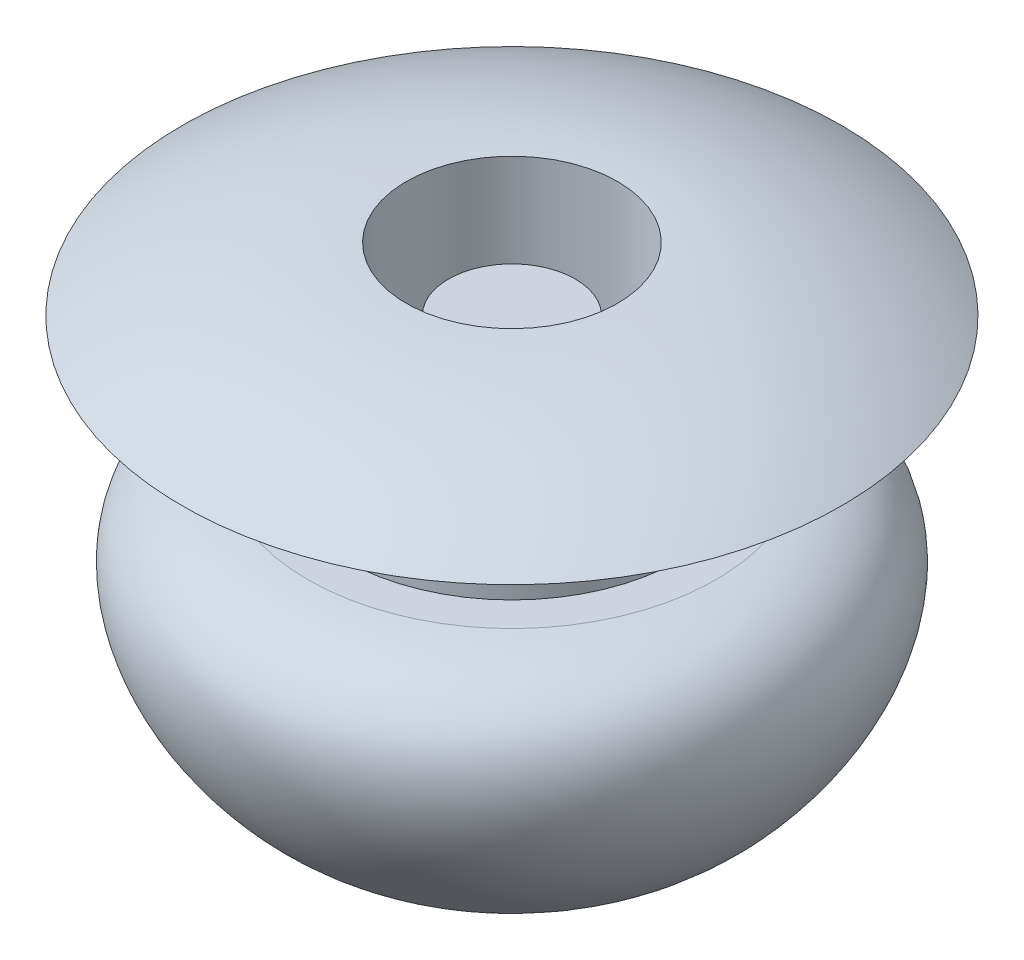
SolidWorks part; units mm, degrees
material "AISI 316 Stal nierdzewna odprężona (SS)"
ref_plane "Płaszczyzna przednia" through (0, 0, 0) normal (0, 0, 1) x (1, 0, 0)
ref_plane "Płaszczyzna górna" through (0, 0, 0) normal (0, 1, 0) x (1, 0, 0)
ref_plane "Płaszczyzna prawa" through (0, 0, 0) normal (1, 0, 0) x (0, 0, -1)
sketch "Szkic1" plane through (0, 0, 0) normal (1, 0, 0) x (0, 0, -1)
  line L1 (0, 0) -> (-0.75, 0)
  line L2 (-0.75, 0) -> (-0.75, -1.7007)
  line L3 (-0.75, -1.7007) -> (-1.25, -1.7007)
  line L4 (-1.25, -1.7007) -> (-1.25, 0.75)
  line L5 (-3.9, 0) -> (-2, 0)
  line L6 (-2, 0) -> (-2, -1.5)
  line L7 (-2, -1.5) -> (-2.4139, -1.5)
  line L8 (0, 0) -> (0, 0.4842) construction
  line L9 (0, -1.7007) -> (0, 0)
  line L10 (0, -1.7007) -> (0, -3.2007)
  line L11 (-10.4007, -1.5) -> (-6.4007, -1.5) construction
  arc A0 (-1.25, 0.75) -> (-3.9, 0) centre (-1.25, -4.3067) ccw
  ellipse E0 centre (0, -2.4507) end of major axis (1.75, -2.4507) minor radius 0.75 (-0.956, -3.0789) -> (0, -3.2007) ccw
  spline S0 degree 3 poles (-2.4139, -1.5) (-3.8675, -1.6697) (-3.5289, -3.802) (-1.084, -5.3735) (-0.2718, -3.3749) (-0.956, -3.0789) knots 0 0 0 0 0.464993 0.721928 1 1 1 1
  dimension "D1" = 7.8
  dimension "D2" = 2.5
  dimension "D3" = 4
  dimension "D4" = 0.75
  dimension "D5" = 1.5
  dimension "D6" = 1.5
  dimension "D7" = 3.5
  dimension "D8" = 3.1855
  dimension "D9" = 2.5026
  dimension "D10" = 1.9
  dimension "D11" = 1.5789
  dimension "D12" = 0.5792
  dimension "D13" = 4.8278
  dimension "D14" = 3.3858
  dimension "D15" = 2.8395
  dimension "D16" = 1.25
  dimension "D17" = 0.6409
  dimension "D18" = 0.956
revolve "Obrót1" add sketch "Szkic1" angle 360 about L8
